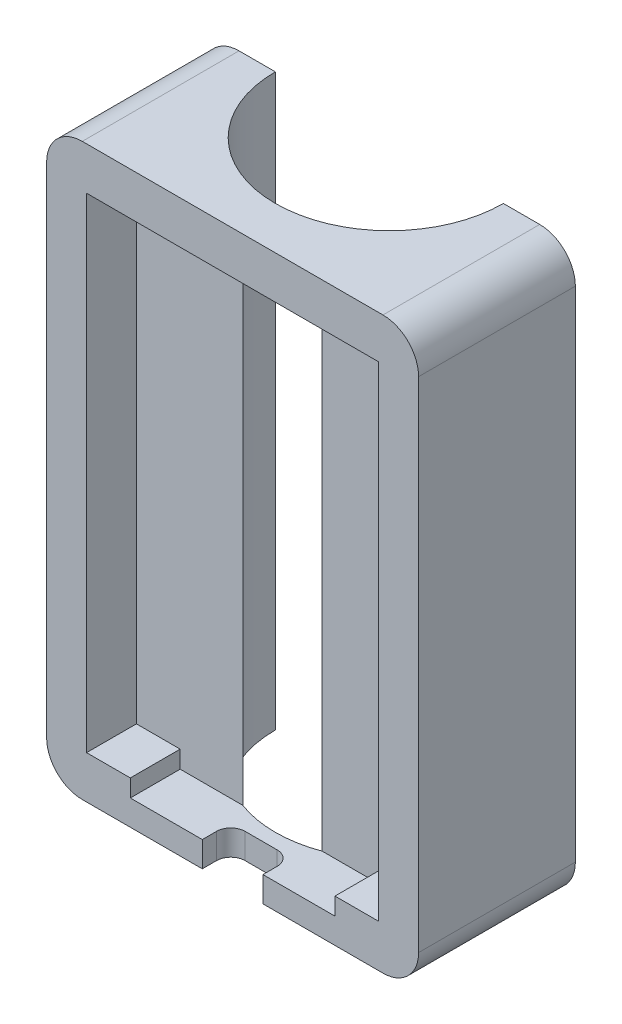
SolidWorks part; units mm, degrees
ref_plane "Plan de face" through (0, 0, 0) normal (0, 0, 1) x (1, 0, 0)
ref_plane "Plan de dessus" through (0, 0, 0) normal (0, 1, 0) x (1, 0, 0)
ref_plane "Plan de droite" through (0, 0, 0) normal (1, 0, 0) x (0, 0, -1)
sketch "Esquisse1" plane through (0, 0, 0) normal (0, 0, 1) x (1, 0, 0)
  line L1 (-41.2248, -2.0065) -> (10.9752, -2.0065)
  line L2 (-41.2248, -2.0065) -> (-41.2248, -82.0065)
  line L3 (-41.2248, -82.0065) -> (10.9752, -82.0065)
  line L4 (10.9752, -2.0065) -> (10.9752, -82.0065)
extrude "Boss.-Extru.2" add sketch "Esquisse1" along normal blind 22
sketch "Esquisse2" plane through (0, -82.0065, 0) normal (0, -1, 0) x (1, 0, 0)
  line L0 (-41.2248, 0) -> (10.9752, 0) construction
  circle A0 centre (-15.1248, 0) radius 16
sketch "Esquisse3" plane through (0, 0, 22) normal (0, 0, 1) x (1, 0, 0)
  line L0 (-41.2248, -2.0065) -> (-41.2248, -82.0065) construction
  line L1 (-39.4848, -5.5677) -> (9.2352, -5.5677)
  line L2 (-39.4848, -5.5677) -> (-39.4848, -78.4453)
  line L3 (-39.4848, -78.4453) -> (9.2352, -78.4453)
  line L4 (9.2352, -5.5677) -> (9.2352, -78.4453)
  line L5 (10.9752, -82.0065) -> (10.9752, -2.0065) construction
  line L6 (10.9752, -2.0065) -> (-41.2248, -2.0065) construction
  line L7 (-31.1248, -82.0065) -> (0.8752, -82.0065) construction
  dimension "D1" = 1.74
  dimension "D2" = 1.74
  dimension "D3" = 3.5612
  dimension "D4" = 3.5612
extrude "Enlèv. mat.-Extru.1" cut sketch "Esquisse3" against normal blind 5
fillet "Congé1" radius 10 4 edges at (-39.4848, -78.4453, 19.5) (9.2352, -78.4453, 19.5) (9.2352, -5.5677, 19.5) (-39.4848, -5.5677, 19.5)
fillet "Congé2" radius 5 4 edges at (-41.2248, -82.0065, 11) (10.9752, -82.0065, 11) (10.9752, -2.0065, 11) (-41.2248, -2.0065, 11)
sketch "Esquisse5" plane through (0, 0, 17) normal (0, 0, 1) x (1, 0, 0)
  line L0 (-35.6248, -42.0065) -> (5.3752, -42.0065) construction
  line L1 (-35.6248, -8.0065) -> (5.3752, -8.0065)
  line L2 (-35.6248, -8.0065) -> (-35.6248, -15.5677)
  line L3 (-35.6248, -76.0065) -> (-29.4848, -76.0065)
  line L4 (5.3752, -8.0065) -> (5.3752, -15.5677)
  line L5 (5.9752, -2.0065) -> (-36.2248, -2.0065) construction
  line L6 (5.3752, -68.4453) -> (5.3752, -76.0065)
  line L7 (-0.7648, -76.0065) -> (5.3752, -76.0065)
  line L8 (-29.4848, -8.0065) -> (-0.7648, -8.0065)
  line L9 (10.9752, -77.0065) -> (10.9752, -7.0065) construction
  line L10 (-35.6248, -68.4453) -> (-35.6248, -15.5677)
  line L11 (5.3752, -15.5677) -> (5.3752, -68.4453)
  line L13 (-35.6248, -15.5677) -> (-35.6248, -8.0065)
  line L15 (-29.4848, -8.0065) -> (-35.6248, -8.0065)
  line L16 (-39.4848, -15.5677) -> (-39.4848, -5.5677)
  line L17 (-39.4848, -5.5677) -> (-29.4848, -5.5677)
  line L18 (-15.1248, -8.0065) -> (-15.1248, -76.0065) construction
  line L26 (9.2352, -15.5677) -> (9.2352, -5.5677)
  line L27 (9.2352, -5.5677) -> (-0.7648, -5.5677)
  line L29 (9.2352, -68.4453) -> (9.2352, -78.4453)
  line L30 (9.2352, -78.4453) -> (-0.7648, -78.4453)
  line L31 (-0.7648, -78.4453) -> (-0.7648, -76.0065)
  line L33 (-29.4848, -78.4453) -> (-29.4848, -76.0065)
  line L34 (-39.4848, -78.4453) -> (-29.4848, -78.4453)
  line L35 (-39.4848, -68.4453) -> (-39.4848, -78.4453)
  line L36 (-35.6248, -68.4453) -> (-35.6248, -76.0065)
  line M5 (-39.4848, -15.5677) -> (-39.4848, -68.4453)
  arc M6 (-39.4848, -68.4453) -> (-29.4848, -78.4453) centre (-29.4848, -68.4453) ccw
  arc M8 (-0.7648, -78.4453) -> (9.2352, -68.4453) centre (-0.7648, -68.4453) ccw
  line M9 (9.2352, -68.4453) -> (9.2352, -15.5677)
  arc M10 (9.2352, -15.5677) -> (-0.7648, -5.5677) centre (-0.7648, -15.5677) ccw
  line M11 (-0.7648, -5.5677) -> (-29.4848, -5.5677)
  arc M12 (-29.4848, -5.5677) -> (-39.4848, -15.5677) centre (-29.4848, -15.5677) ccw
  dimension "D1" = 41
  dimension "D2" = 68
  dimension "D3" = 6
  dimension "D4" = 5.6
extrude "Boss.-Extru.4" add sketch "Esquisse5" along normal blind 5 contours L36 L10 L2 L1 L4 L11 L6 L7 L31 L33 L3 M8 M9 M10 M11 M12 M5 M6 region at (-36.5014, -11.7871, 17)
extrude "Enlèv. mat.-Extru.3" cut sketch "Esquisse2" against normal through all contours A0
sketch "Esquisse7" plane through (0, 0, 17) normal (0, 0, 1) x (1, 0, 0)
  line L0 (-35.6248, -8.0065) -> (5.3752, -8.0065)
  line L1 (5.3752, -8.0065) -> (5.3752, -76.0065)
  line L2 (5.3752, -76.0065) -> (-0.7648, -76.0065)
  line L3 (-0.7648, -76.0065) -> (-0.7648, -78.4453)
  line L4 (-0.7648, -78.4453) -> (-29.4848, -78.4453)
  line L5 (-29.4848, -78.4453) -> (-29.4848, -76.0065)
  line L6 (-29.4848, -76.0065) -> (-35.6248, -76.0065)
  line L7 (-35.6248, -76.0065) -> (-35.6248, -8.0065)
extrude "Enlèv. mat.-Extru.5" cut sketch "Esquisse7" against normal blind 2
sketch "Esquisse8" plane through (0, 0, 22) normal (0, 0, 1) x (1, 0, 0)
  line L1 (-19.3798, -78.4453) -> (-10.8698, -78.4453)
  line L2 (-19.3798, -78.4453) -> (-19.3798, -82.0065)
  line L3 (-19.3798, -82.0065) -> (-10.8698, -82.0065)
  line L4 (-10.8698, -78.4453) -> (-10.8698, -82.0065)
  line L7 (-0.7648, -78.4453) -> (-0.7648, -76.0065) construction
  line L8 (-29.4848, -76.0065) -> (-29.4848, -78.4453) construction
  dimension "D1" = 10.105
  dimension "D2" = 10.105
extrude "Enlèv. mat.-Extru.6" cut sketch "Esquisse8" against normal blind 4
fillet "Congé3" radius 2 2 edges at (-10.8698, -80.2259, 18) (-19.3798, -80.2259, 18)
sketch "Esquisse16" plane through (0, 0, 22) normal (0, 0, 1) x (1, 0, 0)
  circle A0 centre (-37.211, -5.3627) radius 3.0831
  arc A1 (-36.2248, -2.0065) -> (-41.2248, -7.0065) centre (-36.2248, -7.0065) ccw construction
  point P7 (0, 0)
  point P8 (0, 0)
  point P9 (0, 0)
